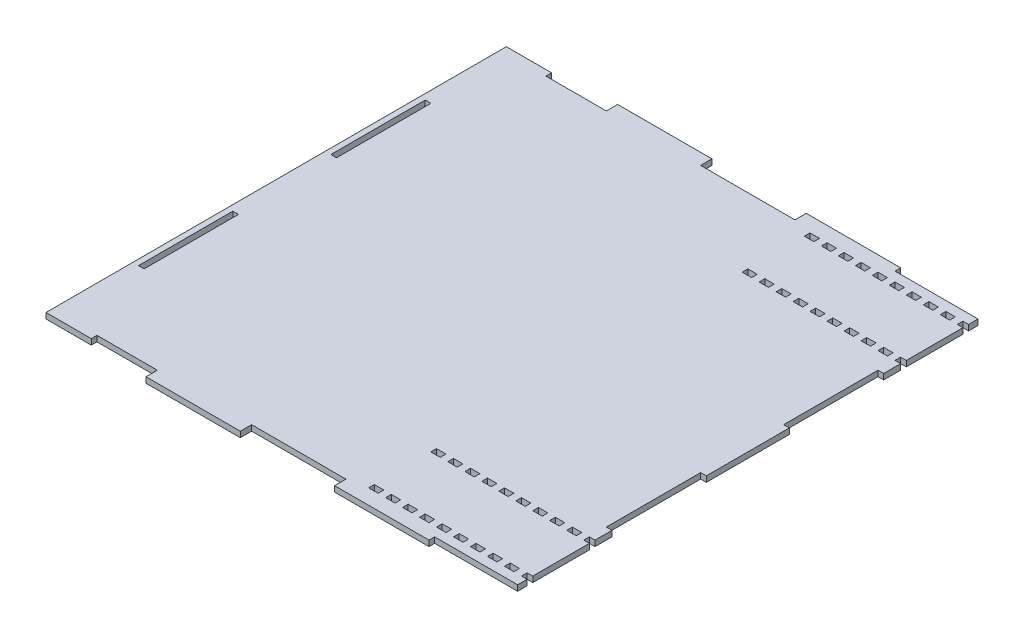
SolidWorks part; units mm, degrees
ref_plane "Front Plane" through (0, 0, 0) normal (0, 0, 1) x (1, 0, 0)
ref_plane "Top Plane" through (0, 0, 0) normal (0, 1, 0) x (1, 0, 0)
ref_plane "Right Plane" through (0, 0, 0) normal (1, 0, 0) x (0, 0, -1)
sketch "Sketch1" plane through (0, 0, 0) normal (0, 1, 0) x (1, 0, 0)
  line L0 (247, -244) -> (247, -239)
  line L1 (0, -244) -> (21, -244)
  line L2 (0, -148) -> (0, -198)
  line L3 (0, 0) -> (21, 0)
  line L4 (53, 3) -> (53, -3)
  line L5 (244, -194) -> (244, -144)
  line L6 (103, 3) -> (103, -3)
  line L7 (53, 3) -> (103, 3)
  line L8 (153, -3) -> (153, 3)
  line L9 (235, -5) -> (240, -5)
  line L10 (203, 0) -> (247, 0)
  line L11 (235, -5) -> (235, -8)
  line L12 (235, -8) -> (240, -8)
  line L13 (203, -244) -> (247, -244)
  line L14 (203, -244) -> (203, -247)
  line L15 (153, -247) -> (203, -247)
  line L16 (247, -50) -> (247, -41)
  line L17 (0, -46) -> (3, -46)
  line L18 (3, -198) -> (0, -198)
  line L19 (0, -96) -> (3, -96)
  line L20 (3, -46) -> (3, -96)
  line L21 (240, -5) -> (240, -8)
  line L22 (53, -241) -> (53, -247)
  line L23 (103, -247) -> (53, -247)
  line L24 (244, -100) -> (244, -50)
  line L25 (103, -247) -> (103, -241)
  line L26 (203, 3) -> (203, 0)
  line L27 (153, 3) -> (203, 3)
  line L28 (103, -241) -> (153, -241)
  line L29 (244, -236) -> (247, -236)
  line L30 (244, -236) -> (244, -239)
  line L31 (244, -5) -> (247, -5)
  line L32 (244, -5) -> (244, -8)
  line L33 (0, -148) -> (3, -148)
  line L34 (153, -247) -> (153, -241)
  line L35 (244, -100) -> (247, -100)
  line L36 (3, -148) -> (3, -198)
  line L37 (247, -5) -> (247, 0)
  line L38 (247, -236) -> (247, -206)
  line L39 (235, -38) -> (240, -38)
  line L40 (0, 0) -> (-3, 0)
  line L41 (0, -46) -> (0, -96)
  line L42 (0, -244) -> (-3, -244)
  line L43 (-3, 0) -> (-3, -244)
  line L44 (244, -144) -> (247, -144)
  line L45 (247, -100) -> (247, -144)
  line L46 (226, -5) -> (231, -5)
  line L47 (226, -5) -> (226, -8)
  line L48 (226, -8) -> (231, -8)
  line L49 (231, -5) -> (231, -8)
  line L50 (217, -5) -> (222, -5)
  line L51 (217, -5) -> (217, -8)
  line L52 (217, -8) -> (222, -8)
  line L53 (222, -5) -> (222, -8)
  line L54 (208, -5) -> (213, -5)
  line L55 (244, -194) -> (247, -194)
  line L56 (208, -5) -> (208, -8)
  line L57 (244, -50) -> (247, -50)
  line L58 (208, -8) -> (213, -8)
  line L59 (213, -5) -> (213, -8)
  line L60 (199, -5) -> (204, -5)
  line L61 (199, -5) -> (199, -8)
  line L62 (53, -3) -> (21, -3)
  line L63 (21, 0) -> (21, -3)
  line L64 (199, -8) -> (204, -8)
  line L65 (204, -5) -> (204, -8)
  line L66 (190, -5) -> (195, -5)
  line L67 (103, -3) -> (153, -3)
  line L68 (190, -5) -> (190, -8)
  line L69 (244, -239) -> (247, -239)
  line L70 (235, -236) -> (240, -236)
  line L71 (235, -236) -> (235, -239)
  line L72 (235, -239) -> (240, -239)
  line L73 (240, -236) -> (240, -239)
  line L74 (190, -8) -> (195, -8)
  line L75 (21, -244) -> (21, -241)
  line L76 (244, -8) -> (247, -8)
  line L77 (195, -5) -> (195, -8)
  line L78 (21, -241) -> (53, -241)
  line L79 (181, -5) -> (186, -5)
  line L80 (181, -5) -> (181, -8)
  line L81 (181, -8) -> (186, -8)
  line L82 (186, -5) -> (186, -8)
  line L83 (172, -5) -> (177, -5)
  line L84 (172, -5) -> (172, -8)
  line L85 (172, -8) -> (177, -8)
  line L86 (177, -5) -> (177, -8)
  line L87 (163, -5) -> (168, -5)
  line L88 (163, -5) -> (163, -8)
  line L89 (163, -8) -> (168, -8)
  line L90 (168, -5) -> (168, -8)
  line L91 (190, -236) -> (195, -236)
  line L92 (190, -236) -> (190, -239)
  line L93 (190, -239) -> (195, -239)
  line L94 (195, -236) -> (195, -239)
  line L95 (199, -236) -> (204, -236)
  line L96 (199, -236) -> (199, -239)
  line L97 (199, -239) -> (204, -239)
  line L98 (204, -236) -> (204, -239)
  line L99 (208, -236) -> (213, -236)
  line L100 (208, -236) -> (208, -239)
  line L101 (208, -239) -> (213, -239)
  line L102 (213, -236) -> (213, -239)
  line L103 (217, -236) -> (222, -236)
  line L104 (217, -236) -> (217, -239)
  line L105 (217, -239) -> (222, -239)
  line L106 (222, -236) -> (222, -239)
  line L107 (226, -236) -> (231, -236)
  line L108 (226, -236) -> (226, -239)
  line L109 (226, -239) -> (231, -239)
  line L110 (231, -236) -> (231, -239)
  line L111 (181, -236) -> (186, -236)
  line L112 (181, -236) -> (181, -239)
  line L113 (181, -239) -> (186, -239)
  line L114 (186, -236) -> (186, -239)
  line L115 (172, -236) -> (177, -236)
  line L116 (172, -236) -> (172, -239)
  line L117 (172, -239) -> (177, -239)
  line L118 (177, -236) -> (177, -239)
  line L119 (163, -236) -> (168, -236)
  line L120 (163, -236) -> (163, -239)
  line L121 (163, -239) -> (168, -239)
  line L122 (168, -236) -> (168, -239)
  line L123 (235, -38) -> (235, -41)
  line L124 (235, -41) -> (240, -41)
  line L125 (240, -38) -> (240, -41)
  line L126 (226, -38) -> (231, -38)
  line L127 (226, -38) -> (226, -41)
  line L128 (226, -41) -> (231, -41)
  line L129 (231, -38) -> (231, -41)
  line L130 (217, -38) -> (222, -38)
  line L131 (217, -38) -> (217, -41)
  line L132 (217, -41) -> (222, -41)
  line L133 (222, -38) -> (222, -41)
  line L134 (208, -38) -> (213, -38)
  line L135 (208, -38) -> (208, -41)
  line L136 (208, -41) -> (213, -41)
  line L137 (213, -38) -> (213, -41)
  line L138 (199, -38) -> (204, -38)
  line L139 (199, -38) -> (199, -41)
  line L140 (199, -41) -> (204, -41)
  line L141 (204, -38) -> (204, -41)
  line L142 (190, -38) -> (195, -38)
  line L143 (190, -38) -> (190, -41)
  line L144 (190, -41) -> (195, -41)
  line L145 (195, -38) -> (195, -41)
  line L146 (181, -38) -> (186, -38)
  line L147 (181, -38) -> (181, -41)
  line L148 (181, -41) -> (186, -41)
  line L149 (186, -38) -> (186, -41)
  line L150 (172, -38) -> (177, -38)
  line L151 (172, -38) -> (172, -41)
  line L152 (172, -41) -> (177, -41)
  line L153 (177, -38) -> (177, -41)
  line L154 (163, -38) -> (168, -38)
  line L155 (163, -38) -> (163, -41)
  line L156 (163, -41) -> (168, -41)
  line L157 (168, -38) -> (168, -41)
  line L158 (247, -38) -> (247, -8)
  line L159 (247, -38) -> (244, -38)
  line L160 (235, -203) -> (240, -203)
  line L161 (247, -41) -> (244, -41)
  line L162 (244, -38) -> (244, -41)
  line L163 (235, -203) -> (235, -206)
  line L164 (235, -206) -> (240, -206)
  line L165 (240, -203) -> (240, -206)
  line L166 (226, -203) -> (231, -203)
  line L167 (226, -203) -> (226, -206)
  line L168 (226, -206) -> (231, -206)
  line L169 (231, -203) -> (231, -206)
  line L170 (217, -203) -> (222, -203)
  line L171 (217, -203) -> (217, -206)
  line L172 (217, -206) -> (222, -206)
  line L173 (222, -203) -> (222, -206)
  line L174 (208, -203) -> (213, -203)
  line L175 (208, -203) -> (208, -206)
  line L176 (208, -206) -> (213, -206)
  line L177 (213, -203) -> (213, -206)
  line L178 (199, -203) -> (204, -203)
  line L179 (199, -203) -> (199, -206)
  line L180 (199, -206) -> (204, -206)
  line L181 (204, -203) -> (204, -206)
  line L182 (190, -203) -> (195, -203)
  line L183 (190, -203) -> (190, -206)
  line L184 (190, -206) -> (195, -206)
  line L185 (195, -203) -> (195, -206)
  line L186 (181, -203) -> (186, -203)
  line L187 (181, -203) -> (181, -206)
  line L188 (181, -206) -> (186, -206)
  line L189 (186, -203) -> (186, -206)
  line L190 (172, -203) -> (177, -203)
  line L191 (172, -203) -> (172, -206)
  line L192 (172, -206) -> (177, -206)
  line L193 (177, -203) -> (177, -206)
  line L194 (163, -203) -> (168, -203)
  line L195 (163, -203) -> (163, -206)
  line L196 (163, -206) -> (168, -206)
  line L197 (168, -203) -> (168, -206)
  line L198 (244, -203) -> (244, -206)
  line L199 (244, -203) -> (247, -203)
  line L200 (247, -203) -> (247, -194)
  line L201 (247, -206) -> (244, -206)
  dimension "D48" = 4
  dimension "D1" = 247
  dimension "D3" = 50
  dimension "D5" = 52
  dimension "D6" = 50
  dimension "D7" = 3
  dimension "D8" = 6
  dimension "D9" = 44
  dimension "D10" = 4
  dimension "D11" = 32
  dimension "D12" = 6
  dimension "D13" = 50
  dimension "D14" = 3
  dimension "D15" = 3
  dimension "D16" = 50
  dimension "D17" = 3
  dimension "D18" = 6
  dimension "D19" = 3
  dimension "D20" = 5
  dimension "D21" = 3
  dimension "D22" = 5
  dimension "D23" = 4
  dimension "D24" = 42
  dimension "D25" = 244
  dimension "D26" = 3
  dimension "D27" = 46
  dimension "D28" = 3
  dimension "D29" = 44
  dimension "D30" = 3
  dimension "D31" = 3
  dimension "D32" = 21
  dimension "D33" = 5
  dimension "D34" = 3
  dimension "D35" = 3
  dimension "D36" = 50
  dimension "D37" = 42
  dimension "D38" = 5
  dimension "D39" = 44
  dimension "D40" = 32
  dimension "D41" = 21
  dimension "D42" = 50
  dimension "D43" = 50
  dimension "D44" = 50
  dimension "D45" = 50
  dimension "D46" = 5
  dimension "D47" = 4
  dimension "D49" = 4
  dimension "D50" = 4
  dimension "D51" = 4
  dimension "D52" = 5
  dimension "D53" = 5
  dimension "D54" = 5
  dimension "D55" = 5
  dimension "D56" = 5
  dimension "D57" = 2
  dimension "D58" = 2
  dimension "D59" = 5
  dimension "D60" = 4
  dimension "D61" = 4
  dimension "D62" = 4
  dimension "D63" = 5
  dimension "D64" = 3
  dimension "D65" = 4
  dimension "D66" = 4
  dimension "D67" = 4
  dimension "D68" = 4
  dimension "D69" = 4
  dimension "D70" = 5
  dimension "D71" = 5
  dimension "D72" = 5
  dimension "D73" = 5
  dimension "D74" = 5
  dimension "D75" = 4
  dimension "D76" = 4
  dimension "D77" = 4
  dimension "D78" = 2
  dimension "D79" = 2
  dimension "D80" = 2
  dimension "D81" = 3
  dimension "D82" = 5
  dimension "D83" = 5
  dimension "D84" = 4
  dimension "D85" = 4
  dimension "D86" = 4
  dimension "D87" = 4
  dimension "D88" = 4
  dimension "D89" = 4
  dimension "D90" = 4
  dimension "D91" = 4
  dimension "D92" = 30
  dimension "D93" = 30
  dimension "D94" = 30
  dimension "D95" = 30
  dimension "D96" = 30
  dimension "D97" = 30
  dimension "D98" = 30
  dimension "D99" = 30
  dimension "D100" = 30
  dimension "D101" = 3
  dimension "D102" = 4
  dimension "D103" = 30
  dimension "D104" = 3
  dimension "D105" = 5
  dimension "D106" = 5
  dimension "D107" = 4
  dimension "D108" = 4
  dimension "D109" = 4
  dimension "D110" = 4
  dimension "D111" = 4
  dimension "D112" = 4
  dimension "D113" = 4
  dimension "D114" = 4
  dimension "D115" = 4
  dimension "D116" = 3
  dimension "D117" = 30
extrude "Boss-Extrude1" add sketch "Sketch1" along normal blind 3
equation "\"w\"=3"
equation "\"L\"=50"
